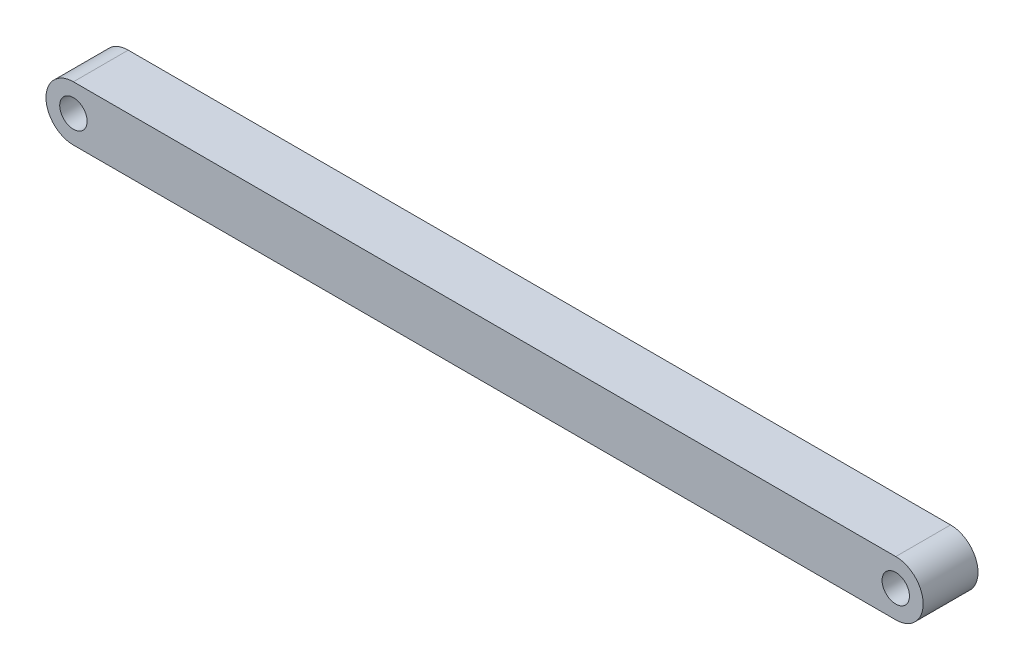
SolidWorks part; units mm, degrees
material "ABS"
ref_plane "Front Plane" through (0, 0, 0) normal (0, 0, 1) x (1, 0, 0)
ref_plane "Top Plane" through (0, 0, 0) normal (0, 1, 0) x (1, 0, 0)
ref_plane "Right Plane" through (0, 0, 0) normal (1, 0, 0) x (0, 0, -1)
ref_axis "X" through (-88.99, 0, 0) along (1, 0, 0)
ref_axis "Y" through (0, 55, 0) along (0, -1, 0)
ref_axis "Z" through (0, 0, -88.99) along (0, 0, 1)
sketch "Sketch1" plane through (0, 0, 0) normal (0, 0, 1) x (1, 0, 0)
  line L0 (0, 0) -> (150, 0) construction
  line L1 (0, 5) -> (150, 5)
  line L2 (0, -5) -> (150, -5)
  arc A0 (0, 5) -> (0, -5) centre (0, 0) ccw
  arc A1 (150, -5) -> (150, 5) centre (150, 0) ccw
  circle A2 centre (0, 0) radius 2.5
  circle A3 centre (150, 0) radius 2.5
  point P3 (75, 0)
  dimension "D1" = 5
  dimension "D3" = 5
  dimension "D2" = 150
extrude "Boss-Extrude1" add sketch "Sketch1" along normal mid plane 10
sketch "Sketch2" [suppressed] plane through (0, 0, 0) normal (0, 0, 1) x (1, 0, 0)
  line L0 (0, 5) -> (-19.8809, 5)
  line L1 (0, -5) -> (-19.8809, -5)
  line L2 (0, 0) -> (-14.4957, 14.4957) construction
  line L3 (0, 0) -> (-8.6637, -18.5793) construction
  line L4 (0, 0) -> (150, 0) construction
  line L5 (-14.4957, 14.4957) -> (-18.7383, 18.7383)
  line L6 (-8.6637, -18.5793) -> (-11.1994, -24.0172)
  arc A0 (-19.8809, 5) -> (-14.4957, 14.4957) centre (0, 0) cw
  arc A1 (-19.8809, -5) -> (-8.6637, -18.5793) centre (0, 0) ccw
  arc A3 (-18.7383, 18.7383) -> (-11.1994, -24.0172) centre (0, 0) ccw
  arc A4 (0, 5) -> (0, -5) centre (0, 0) ccw construction
  arc A5 (0, 5) -> (0, -5) centre (0, 0) ccw
  dimension "D1" = 135
  dimension "D3" = 20.5
  dimension "D2" = 110
  dimension "D4" = 6
extrude "Boss-Extrude2" [suppressed] add sketch "Sketch2" along normal up to surface and the other way up to surface
fillet "Fillet1" [suppressed] radius 4
sketch "Sketch3" [suppressed] plane through (0, 0, 0) normal (0, 0, 1) x (1, 0, 0)
  line L0 (-20.0217, 18.8501) -> (-18.7383, 18.7383)
  line L1 (-11.7405, -24.8668) -> (-11.1994, -24.0172)
  arc A1 (-18.7383, 18.7383) -> (-11.1994, -24.0172) centre (0, 0) ccw construction
  arc A2 (-18.7383, 18.7383) -> (-11.1994, -24.0172) centre (0, 0) ccw
  arc A121 (-31.9856, -0.9598) -> (-27.4055, -2.2658) centre (-26.4703, 9.6977) ccw
  arc A122 (-27.4055, -2.2658) -> (-27.1931, -4.0906) centre (0, 0) ccw
  arc A123 (-27.1931, -4.0906) -> (-31.3506, -6.4139) centre (-23.5345, -15.5193) ccw
  arc A124 (-31.3506, -6.4139) -> (-31.0871, -7.589) centre (0, 0) ccw
  arc A125 (-31.0871, -7.589) -> (-26.3355, -7.9142) centre (-27.9081, 3.9823) ccw
  arc A126 (-26.3355, -7.9142) -> (-25.7483, -9.655) centre (0, 0) ccw
  arc A127 (-25.7483, -9.655) -> (-29.332, -12.7919) centre (-19.7936, -20.0732) ccw
  arc A128 (-29.332, -12.7919) -> (-28.8299, -13.8865) centre (0, 0) ccw
  arc A129 (-28.8299, -13.8865) -> (-24.1146, -13.2167) centre (-28.1262, -1.9071) ccw
  arc A130 (-24.1146, -13.2167) -> (-23.1783, -14.7974) centre (0, 0) ccw
  arc A131 (-23.1783, -14.7974) -> (-26.0315, -18.6108) centre (-15.1876, -23.7499) ccw
  arc A132 (-26.0315, -18.6108) -> (-25.3128, -19.5771) centre (0, 0) ccw
  arc A133 (-25.3128, -19.5771) -> (-20.8397, -17.9416) centre (-27.1151, -7.7132) ccw
  arc A134 (-20.8397, -17.9416) -> (-19.5953, -19.293) centre (0, 0) ccw
  arc A135 (-19.5953, -19.293) -> (-21.5932, -23.6164) centre (-9.9178, -26.3886) ccw
  arc A136 (-21.5932, -23.6164) -> (-20.6893, -24.4121) centre (0, 0) ccw
  arc A137 (-20.6893, -24.4121) -> (-16.654, -21.8824) centre (-24.9189, -13.1822) ccw
  arc A138 (-16.654, -21.8824) -> (-15.1558, -22.9455) centre (0, 0) ccw
  arc A139 (-15.1558, -22.9455) -> (-16.2112, -27.5898) centre (-4.2146, -27.874) ccw
  arc A140 (-16.2112, -27.5898) -> (-15.1616, -28.1802) centre (0, 0) ccw
  arc A141 (-15.1616, -28.1802) -> (-11.7405, -24.8668) centre (-21.6336, -18.0751) ccw
  arc A142 (-11.7405, -24.8668) -> (-10.054, -25.5952) centre (0, 0) ccw
  arc A143 (-10.054, -25.5952) -> (-10.1207, -30.3574) centre (1.6728, -28.1411) ccw
  arc A144 (-10.1207, -30.3574) -> (-8.9713, -30.7167) centre (0, 0) ccw
  arc A145 (-8.9713, -30.7167) -> (-6.3138, -26.7643) centre (-17.4028, -22.178) ccw
  arc A146 (-6.3138, -26.7643) -> (-4.5127, -27.1262) centre (0, 0) ccw
  arc A147 (-4.5127, -27.1262) -> (-3.5879, -31.7982) centre (7.4872, -27.1783) ccw
  arc A148 (-3.5879, -31.7982) -> (-2.3889, -31.9107) centre (0, 0) ccw
  arc A149 (-2.3889, -31.9107) -> (-0.6113, -27.4922) centre (-12.4115, -25.3116) ccw
  arc A150 (-0.6113, -27.4922) -> (1.2257, -27.4717) centre (0, 0) ccw
  arc A151 (1.2257, -27.4717) -> (3.1017, -31.8493) centre (12.9742, -25.0278) ccw
  arc A152 (3.1017, -31.8493) -> (4.2979, -31.7101) centre (0, 0) ccw
  arc A153 (4.2979, -31.7101) -> (5.1181, -27.0185) centre (-6.8777, -27.3389) ccw
  arc A154 (5.1181, -27.0185) -> (6.9106, -26.6165) centre (0, 0) ccw
  arc A155 (6.9106, -26.6165) -> (9.6558, -30.5085) centre (17.8943, -21.7834) ccw
  arc A156 (9.6558, -30.5085) -> (10.7969, -30.1235) centre (0, 0) ccw
  arc A157 (10.7969, -30.1235) -> (10.6237, -25.364) centre (-1.0433, -28.1715) ccw
  arc A158 (10.6237, -25.364) -> (12.2935, -24.5981) centre (0, 0) ccw
  arc A159 (12.2935, -24.5981) -> (15.7879, -27.8342) centre (22.0323, -17.5869) ccw
  arc A160 (15.7879, -27.8342) -> (16.824, -27.2205) centre (0, 0) ccw
  arc A161 (16.824, -27.2205) -> (15.665, -22.6009) centre (4.8367, -27.7728) ccw
  arc A162 (15.665, -22.6009) -> (17.1391, -21.5046) centre (0, 0) ccw
  arc A163 (17.1391, -21.5046) -> (21.2299, -23.9435) centre (25.2073, -12.6218) ccw
  arc A164 (21.2299, -23.9435) -> (22.1158, -23.1277) centre (0, 0) ccw
  arc A165 (22.1158, -23.1277) -> (20.0217, -18.8501) centre (10.5053, -26.1603) ccw
  arc A166 (20.0217, -18.8501) -> (21.2356, -17.4712) centre (0, 0) ccw
  arc A167 (21.2356, -17.4712) -> (25.7441, -19.0063) centre (27.2807, -7.1051) ccw
  arc A168 (25.7441, -19.0063) -> (26.441, -18.0242) centre (0, 0) ccw
  arc A169 (26.441, -18.0242) -> (23.5033, -14.2755) centre (15.7147, -23.4044) ccw
  arc A170 (23.5033, -14.2755) -> (24.404, -12.6743) centre (0, 0) ccw
  arc A171 (24.404, -12.6743) -> (29.1332, -13.2385) centre (28.1618, -1.2779) ccw
  arc A172 (29.1332, -13.2385) -> (29.6107, -12.1329) centre (0, 0) ccw
  arc A173 (29.6107, -12.1329) -> (25.9578, -9.0769) centre (20.2374, -19.6257) ccw
  arc A174 (25.9578, -9.0769) -> (26.5059, -7.3235) centre (0, 0) ccw
  arc A175 (26.5059, -7.3235) -> (31.249, -6.8921) centre (27.8121, 4.6052) ccw
  arc A176 (31.249, -6.8921) -> (31.4862, -5.7114) centre (0, 0) ccw
  arc A177 (31.4862, -5.7114) -> (27.2777, -3.4816) centre (23.8756, -14.9892) ccw
  arc A178 (27.2777, -3.4816) -> (27.4493, -1.6526) centre (0, 0) ccw
  arc A179 (27.4493, -1.6526) -> (31.9991, -0.2444) centre (26.2468, 10.2871) ccw
  arc A180 (31.9991, -0.2444) -> (31.9856, 0.9598) centre (0, 0) ccw
  arc A181 (31.9856, 0.9598) -> (27.4055, 2.2658) centre (26.4703, -9.6977) ccw
  arc A182 (27.4055, 2.2658) -> (27.1931, 4.0906) centre (0, 0) ccw
  arc A183 (27.1931, 4.0906) -> (31.3506, 6.4139) centre (23.5345, 15.5193) ccw
  arc A184 (31.3506, 6.4139) -> (31.0871, 7.589) centre (0, 0) ccw
  arc A185 (31.0871, 7.589) -> (26.3355, 7.9142) centre (27.9081, -3.9823) ccw
  arc A186 (26.3355, 7.9142) -> (25.7483, 9.655) centre (0, 0) ccw
  arc A187 (25.7483, 9.655) -> (29.332, 12.7919) centre (19.7936, 20.0732) ccw
  arc A188 (29.332, 12.7919) -> (28.8299, 13.8865) centre (0, 0) ccw
  arc A189 (28.8299, 13.8865) -> (24.1146, 13.2167) centre (28.1262, 1.9071) ccw
  arc A190 (24.1146, 13.2167) -> (23.1783, 14.7974) centre (0, 0) ccw
  arc A191 (23.1783, 14.7974) -> (26.0315, 18.6108) centre (15.1876, 23.7499) ccw
  arc A192 (26.0315, 18.6108) -> (25.3128, 19.5771) centre (0, 0) ccw
  arc A193 (25.3128, 19.5771) -> (20.8397, 17.9416) centre (27.1151, 7.7132) ccw
  arc A194 (20.8397, 17.9416) -> (19.5953, 19.293) centre (0, 0) ccw
  arc A195 (19.5953, 19.293) -> (21.5932, 23.6164) centre (9.9178, 26.3886) ccw
  arc A196 (21.5932, 23.6164) -> (20.6893, 24.4121) centre (0, 0) ccw
  arc A197 (20.6893, 24.4121) -> (16.654, 21.8824) centre (24.9189, 13.1822) ccw
  arc A198 (16.654, 21.8824) -> (15.1558, 22.9455) centre (0, 0) ccw
  arc A199 (15.1558, 22.9455) -> (16.2112, 27.5898) centre (4.2146, 27.874) ccw
  arc A200 (16.2112, 27.5898) -> (15.1616, 28.1802) centre (0, 0) ccw
  arc A201 (15.1616, 28.1802) -> (11.7405, 24.8668) centre (21.6336, 18.0751) ccw
  arc A202 (11.7405, 24.8668) -> (10.054, 25.5952) centre (0, 0) ccw
  arc A203 (10.054, 25.5952) -> (10.1207, 30.3574) centre (-1.6728, 28.1411) ccw
  arc A204 (10.1207, 30.3574) -> (8.9713, 30.7167) centre (0, 0) ccw
  arc A205 (8.9713, 30.7167) -> (6.3138, 26.7643) centre (17.4028, 22.178) ccw
  arc A206 (6.3138, 26.7643) -> (4.5127, 27.1262) centre (0, 0) ccw
  arc A207 (4.5127, 27.1262) -> (3.5879, 31.7982) centre (-7.4872, 27.1783) ccw
  arc A208 (3.5879, 31.7982) -> (2.3889, 31.9107) centre (0, 0) ccw
  arc A209 (2.3889, 31.9107) -> (0.6113, 27.4922) centre (12.4115, 25.3116) ccw
  arc A210 (0.6113, 27.4922) -> (-1.2257, 27.4717) centre (0, 0) ccw
  arc A211 (-1.2257, 27.4717) -> (-3.1017, 31.8493) centre (-12.9742, 25.0278) ccw
  arc A212 (-3.1017, 31.8493) -> (-4.2979, 31.7101) centre (0, 0) ccw
  arc A213 (-4.2979, 31.7101) -> (-5.1181, 27.0185) centre (6.8777, 27.3389) ccw
  arc A214 (-5.1181, 27.0185) -> (-6.9106, 26.6165) centre (0, 0) ccw
  arc A215 (-6.9106, 26.6165) -> (-9.6558, 30.5085) centre (-17.8943, 21.7834) ccw
  arc A216 (-9.6558, 30.5085) -> (-10.7969, 30.1235) centre (0, 0) ccw
  arc A217 (-10.7969, 30.1235) -> (-10.6237, 25.364) centre (1.0433, 28.1715) ccw
  arc A218 (-10.6237, 25.364) -> (-12.2935, 24.5981) centre (0, 0) ccw
  arc A219 (-12.2935, 24.5981) -> (-15.7879, 27.8342) centre (-22.0323, 17.5869) ccw
  arc A220 (-15.7879, 27.8342) -> (-16.824, 27.2205) centre (0, 0) ccw
  arc A221 (-16.824, 27.2205) -> (-15.665, 22.6009) centre (-4.8367, 27.7728) ccw
  arc A222 (-15.665, 22.6009) -> (-17.1391, 21.5046) centre (0, 0) ccw
  arc A223 (-17.1391, 21.5046) -> (-21.2299, 23.9435) centre (-25.2073, 12.6218) ccw
  arc A224 (-21.2299, 23.9435) -> (-22.1158, 23.1277) centre (0, 0) ccw
  arc A225 (-22.1158, 23.1277) -> (-20.0217, 18.8501) centre (-10.5053, 26.1603) ccw
  arc A226 (-20.0217, 18.8501) -> (-21.2356, 17.4712) centre (0, 0) ccw
  arc A227 (-21.2356, 17.4712) -> (-25.7441, 19.0063) centre (-27.2807, 7.1051) ccw
  arc A228 (-25.7441, 19.0063) -> (-26.441, 18.0242) centre (0, 0) ccw
  arc A229 (-26.441, 18.0242) -> (-23.5033, 14.2755) centre (-15.7147, 23.4044) ccw
  arc A230 (-23.5033, 14.2755) -> (-24.404, 12.6743) centre (0, 0) ccw
  arc A231 (-24.404, 12.6743) -> (-29.1332, 13.2385) centre (-28.1618, 1.2779) ccw
  arc A232 (-29.1332, 13.2385) -> (-29.6107, 12.1329) centre (0, 0) ccw
  arc A233 (-29.6107, 12.1329) -> (-25.9578, 9.0769) centre (-20.2374, 19.6257) ccw
  arc A234 (-25.9578, 9.0769) -> (-26.5059, 7.3235) centre (0, 0) ccw
  arc A235 (-26.5059, 7.3235) -> (-31.249, 6.8921) centre (-27.8121, -4.6052) ccw
  arc A236 (-31.249, 6.8921) -> (-31.4862, 5.7114) centre (0, 0) ccw
  arc A237 (-31.4862, 5.7114) -> (-27.2777, 3.4816) centre (-23.8756, 14.9892) ccw
  arc A238 (-27.2777, 3.4816) -> (-27.4493, 1.6526) centre (0, 0) ccw
  arc A239 (-27.4493, 1.6526) -> (-31.9991, 0.2444) centre (-26.2468, -10.2871) ccw
  arc A240 (-31.9991, 0.2444) -> (-31.9856, -0.9598) centre (0, 0) ccw
  arc A241 (-31.9856, -0.9598) -> (-27.4055, -2.2658) centre (-26.4703, 9.6977) ccw
  arc A242 (-27.4055, -2.2658) -> (-27.1931, -4.0906) centre (0, 0) ccw
  arc A243 (-27.1931, -4.0906) -> (-31.3506, -6.4139) centre (-23.5345, -15.5193) ccw
  arc A244 (-31.3506, -6.4139) -> (-31.0871, -7.589) centre (0, 0) ccw
  arc A245 (-31.0871, -7.589) -> (-26.3355, -7.9142) centre (-27.9081, 3.9823) ccw
  arc A246 (-26.3355, -7.9142) -> (-25.7483, -9.655) centre (0, 0) ccw
  arc A247 (-25.7483, -9.655) -> (-29.332, -12.7919) centre (-19.7936, -20.0732) ccw
  arc A248 (-29.332, -12.7919) -> (-28.8299, -13.8865) centre (0, 0) ccw
  arc A249 (-28.8299, -13.8865) -> (-24.1146, -13.2167) centre (-28.1262, -1.9071) ccw
  arc A250 (-24.1146, -13.2167) -> (-23.1783, -14.7974) centre (0, 0) ccw
  arc A251 (-23.1783, -14.7974) -> (-26.0315, -18.6108) centre (-15.1876, -23.7499) ccw
  arc A252 (-26.0315, -18.6108) -> (-25.3128, -19.5771) centre (0, 0) ccw
  arc A253 (-25.3128, -19.5771) -> (-20.8397, -17.9416) centre (-27.1151, -7.7132) ccw
  arc A254 (-20.8397, -17.9416) -> (-19.5953, -19.293) centre (0, 0) ccw
  arc A255 (-19.5953, -19.293) -> (-21.5932, -23.6164) centre (-9.9178, -26.3886) ccw
  arc A256 (-21.5932, -23.6164) -> (-20.6893, -24.4121) centre (0, 0) ccw
  arc A257 (-20.6893, -24.4121) -> (-16.654, -21.8824) centre (-24.9189, -13.1822) ccw
  arc A258 (-16.654, -21.8824) -> (-15.1558, -22.9455) centre (0, 0) ccw
  arc A259 (-15.1558, -22.9455) -> (-16.2112, -27.5898) centre (-4.2146, -27.874) ccw
  arc A260 (-16.2112, -27.5898) -> (-15.1616, -28.1802) centre (0, 0) ccw
  arc A261 (-15.1616, -28.1802) -> (-11.7405, -24.8668) centre (-21.6336, -18.0751) ccw
  arc A346 (-20.0217, 18.8501) -> (-21.2356, 17.4712) centre (0, 0) ccw
  arc A347 (-21.2356, 17.4712) -> (-25.7441, 19.0063) centre (-27.2807, 7.1051) ccw
  arc A348 (-25.7441, 19.0063) -> (-26.441, 18.0242) centre (0, 0) ccw
  arc A349 (-26.441, 18.0242) -> (-23.5033, 14.2755) centre (-15.7147, 23.4044) ccw
  arc A350 (-23.5033, 14.2755) -> (-24.404, 12.6743) centre (0, 0) ccw
  arc A351 (-24.404, 12.6743) -> (-29.1332, 13.2385) centre (-28.1618, 1.2779) ccw
  arc A352 (-29.1332, 13.2385) -> (-29.6107, 12.1329) centre (0, 0) ccw
  arc A353 (-29.6107, 12.1329) -> (-25.9578, 9.0769) centre (-20.2374, 19.6257) ccw
  arc A354 (-25.9578, 9.0769) -> (-26.5059, 7.3235) centre (0, 0) ccw
  arc A355 (-26.5059, 7.3235) -> (-31.249, 6.8921) centre (-27.8121, -4.6052) ccw
  arc A356 (-31.249, 6.8921) -> (-31.4862, 5.7114) centre (0, 0) ccw
  arc A357 (-31.4862, 5.7114) -> (-27.2777, 3.4816) centre (-23.8756, 14.9892) ccw
  arc A358 (-27.2777, 3.4816) -> (-27.4493, 1.6526) centre (0, 0) ccw
  arc A359 (-27.4493, 1.6526) -> (-31.9991, 0.2444) centre (-26.2468, -10.2871) ccw
  arc A360 (-31.9991, 0.2444) -> (-31.9856, -0.9598) centre (0, 0) ccw
  dimension "D1" = 0
extrude "Boss-Extrude3" [suppressed] add sketch "Sketch3" along normal up to surface and the other way up to surface
